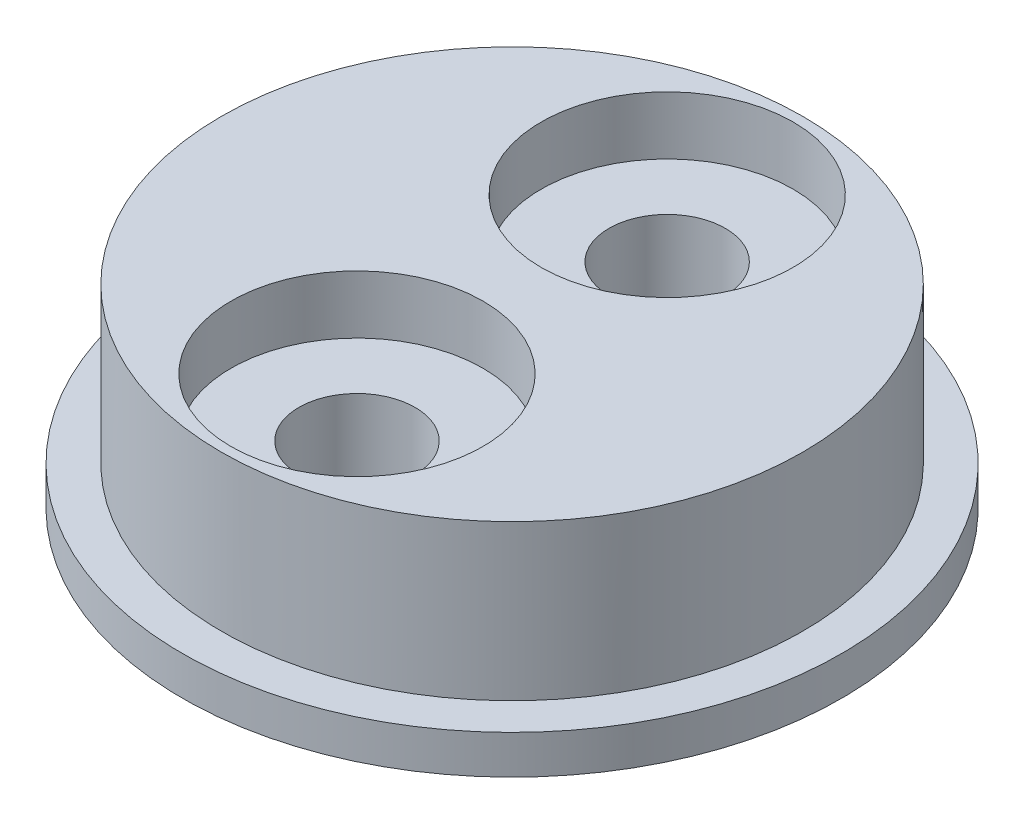
SolidWorks part; units mm, degrees
ref_plane "Front Plane" through (0, 0, 0) normal (0, 0, 1) x (1, 0, 0)
ref_plane "Top Plane" through (0, 0, 0) normal (0, 1, 0) x (1, 0, 0)
ref_plane "Right Plane" through (0, 0, 0) normal (1, 0, 0) x (0, 0, -1)
sketch "Sketch1" plane through (0, 0, 0) normal (0, 1, 0) x (1, 0, 0)
  circle A0 centre (0, 0) radius 7.5
  dimension "D1" = 15
extrude "Boss-Extrude1" add sketch "Sketch1" along normal blind 5
sketch "Sketch2" plane through (0, 5, 0) normal (0, 1, 0) x (1, 0, 0)
  line L0 (0, 7.9744) -> (0, -8.0985) construction
  circle A2 centre (0, 0) radius 4 construction
  circle A3 centre (0, 4) radius 3.25
  circle A4 centre (0, -4) radius 3.25
  point P8 (0, -4)
  point P12 (0, 0)
  dimension "D1" = 8
  dimension "D2" = 6.5
  dimension "D3" = 2
extrude "Cut-Extrude1" cut sketch "Sketch2" against normal blind 1.5
sketch "Sketch4" plane through (0, 0, 0) normal (0, -1, 0) x (1, 0, 0)
  circle A0 centre (0, 0) radius 8.5
  dimension "D1" = 17
extrude "Boss-Extrude2" add sketch "Sketch4" against normal blind 1
sketch "Sketch3" plane through (0, 5, 0) normal (0, 1, 0) x (1, 0, 0)
  line L0 (0, 8.0571) -> (0, -8.4294) construction
  circle A0 centre (0, 4) radius 1.5
  circle A1 centre (0, -4) radius 1.5
  circle A2 centre (0, 0) radius 4 construction
  point P9 (0, -4.0027)
  point P10 (0, -4)
  dimension "D1" = 8
  dimension "D2" = 3
extrude "Cut-Extrude2" cut sketch "Sketch3" against normal through all
